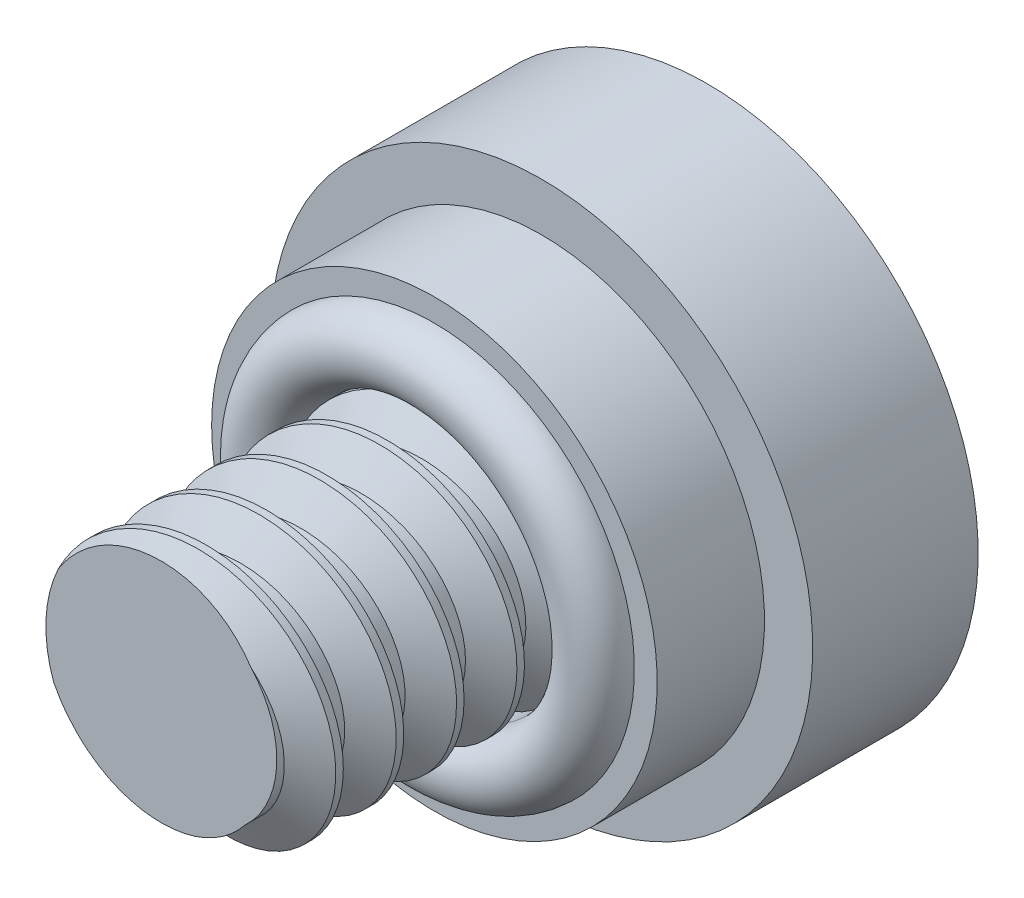
SolidWorks part; units mm, degrees
ref_plane "Front Plane" through (0, 0, 0) normal (0, 0, 1) x (1, 0, 0)
ref_plane "Top Plane" through (0, 0, 0) normal (0, 1, 0) x (1, 0, 0)
ref_plane "Right Plane" through (0, 0, 0) normal (1, 0, 0) x (0, 0, -1)
sketch "Sketch1" plane through (0, 0, 0) normal (0, 0, 1) x (1, 0, 0)
  circle A0 centre (0, 0) radius 2.31
  dimension "D1" = 4.62
extrude "Boss-Extrude1" add sketch "Sketch1" along normal blind 4.5
sketch "Sketch2" plane through (0, 0, 0) normal (0, 1, 0) x (1, 0, 0)
  line L0 (3.505, 0) -> (3.905, 0)
  line L1 (3.905, 0) -> (3.905, 1.88)
  line L2 (3.905, 1.88) -> (4.75, 1.88)
  line L3 (4.75, 1.88) -> (4.75, 4.78)
  line L4 (4.75, 4.78) -> (0.8769, 4.78)
  line L5 (0.8769, 4.78) -> (0.8769, 4.68)
  line L6 (0.8769, 4.68) -> (0, 4.68)
  line L7 (0, 4.68) -> (0, 0) construction
  line L8 (2.31, 0) -> (0, 0)
  line L9 (0, 4.68) -> (0, 0)
  arc A0 (2.31, 0) -> (3.505, 0) centre (2.9075, 0) ccw
  dimension "D1" = 0.1
  dimension "D2" = 9.5
  dimension "D3" = 7.81
  dimension "D4" = 2.9
  dimension "D5" = 4.78
  dimension "D6" = 0.8769
  dimension ".4" = 0.4
revolve "Revolve1" add sketch "Sketch2" angle 360 about L7
thread "Thread1" pitch 1.0583 method cut profile "Thread Profile1" start angle 0, offset 1, length 0, pitch 1.0583, diameter 4.62
ref_plane "Plane1" through (-2.31, 0, 5.5) normal (0, -1, 0) x (-1, 0, 0)
sketch "Thread Profile1" plane through (-2.31, 0, 5.5) normal (0, -1, 0) x (-1, 0, 0)
  line L0 (0, 0) -> (0, 1.0583) construction
  line L11 (0, 0) -> (0, 0.926)
  line L12 (0, 0.926) -> (-0.5728, 0.5953)
  line L13 (-0.5728, 0.5953) -> (-0.5728, 0.3307)
  line L15 (-0.5728, 0.3307) -> (0, 0)
  line L17 (-0.5728, 0.463) -> (0, 0.463) construction
  point P2 (0, 0)
  dimension "Pitch" = 1.0583
  dimension "Profile_Angle" = 60
  dimension "Profile_Land" = 0.2646
  dimension "Profile_Height" = 0.5728
